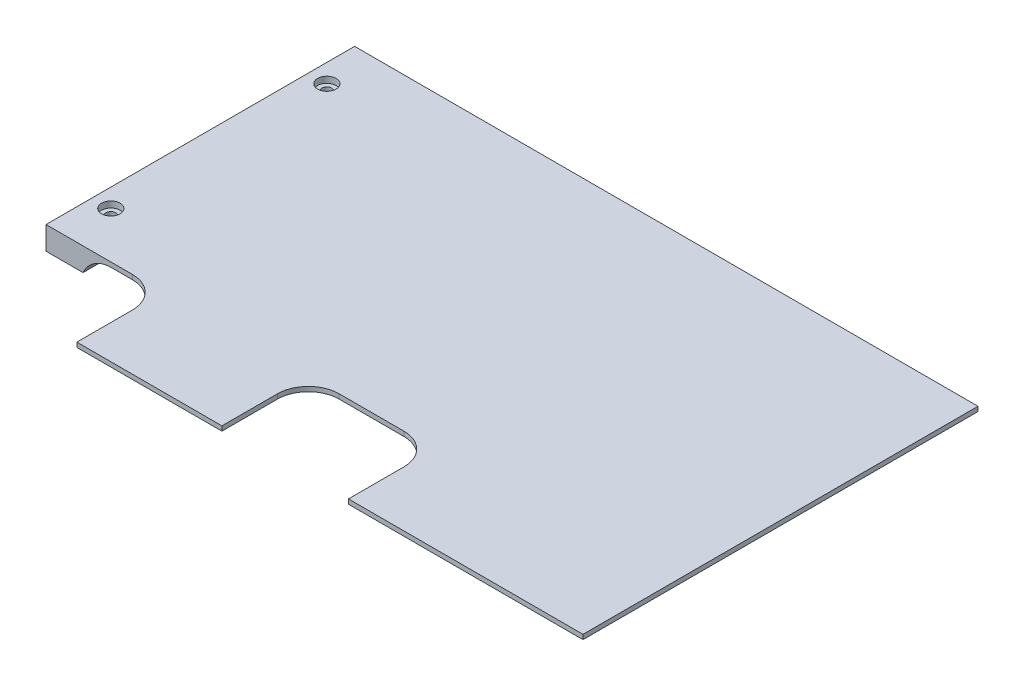
SolidWorks part; units mm, degrees
ref_plane "Alzado" through (0, 0, 0) normal (0, 0, 1) x (1, 0, 0)
ref_plane "Planta" through (0, 0, 0) normal (0, 1, 0) x (1, 0, 0)
ref_plane "Vista lateral" through (0, 0, 0) normal (1, 0, 0) x (0, 0, -1)
sketch "Croquis1" plane through (0, 0, 0) normal (0, 1, 0) x (1, 0, 0)
  line L1 (0, 0) -> (202, 0)
  line L2 (0, 0) -> (0, 100)
  line L3 (0, 100) -> (202, 100)
  line L4 (202, 0) -> (202, 100)
  dimension "D1" = 202
  dimension "D2" = 100
extrude "Saliente-Extruir1" add sketch "Croquis1" along normal blind 1.5
sketch "Croquis2" plane through (0, 1.5, 0) normal (0, 1, 0) x (1, 0, 0)
  line L0 (6, 100) -> (6, 0) construction
  line L1 (202, 100) -> (0, 100) construction
  line L2 (0, 0) -> (202, 0) construction
  line L3 (0, 100) -> (0, 0) construction
  circle A0 centre (6, 85) radius 1.6
  circle A1 centre (6, 15) radius 1.6
  dimension "D2" = 3.2
  dimension "D3" = 3.2
  dimension "D1" = 6
  dimension "D4" = 15
  dimension "D5" = 15
extrude "Cortar-Extruir1" cut sketch "Croquis2" against normal up to surface (1.5 mm away) up to face at (101, 0, -50)
sketch "Croquis3" plane through (0, 0, 0) normal (0, -1, 0) x (1, 0, 0)
  line L0 (0, 0) -> (202, 0) construction
  line L1 (0, -100) -> (12, -100)
  line L2 (0, -100) -> (0, 0)
  line L3 (0, 0) -> (12, 0)
  line L4 (12, -100) -> (12, 0)
  circle A0 centre (6, -15) radius 1.6 construction
  circle A1 centre (6, -85) radius 1.6 construction
  circle A2 centre (6, -15) radius 1.6
  circle A3 centre (6, -85) radius 1.6
  dimension "D1" = 12
extrude "Saliente-Extruir2" add sketch "Croquis3" along normal blind 6
sketch "Croquis4" plane through (0, 1.5, 0) normal (0, 1, 0) x (1, 0, 0)
  line L0 (0, 0) -> (202, 0) construction
  line L1 (38, 0) -> (85, 0)
  line L2 (38, 0) -> (38, -28)
  line L3 (38, -28) -> (85, -28)
  line L4 (85, 0) -> (85, -28)
  line L5 (0, 100) -> (0, 0) construction
  line L6 (202, 0) -> (126, 0)
  line L7 (202, 0) -> (202, -28)
  line L8 (202, -28) -> (126, -28)
  line L9 (126, 0) -> (126, -28)
  dimension "D1" = 28
  dimension "D2" = 28
  dimension "D3" = 38
  dimension "D4" = 76
  dimension "D5" = 47
extrude "Saliente-Extruir3" add sketch "Croquis4" against normal up to surface (1.5 mm away) up to face at (107, 0, -50)
fillet "Redondeo1" radius 10 3 edges at (38, 0.75, 0) (85, 0.75, 0) (126, 0.75, 0)
fillet "Redondeo2" radius 10 1 edges at (12, 0, -50)
sketch "Croquis5" plane through (0, 1.5, 0) normal (0, 1, 0) x (1, 0, 0)
  circle A0 centre (6, 85) radius 3
  circle A1 centre (6, 15) radius 3
  dimension "D1" = 6
  dimension "D2" = 6
extrude "Cortar-Extruir2" cut sketch "Croquis5" against normal blind 2
